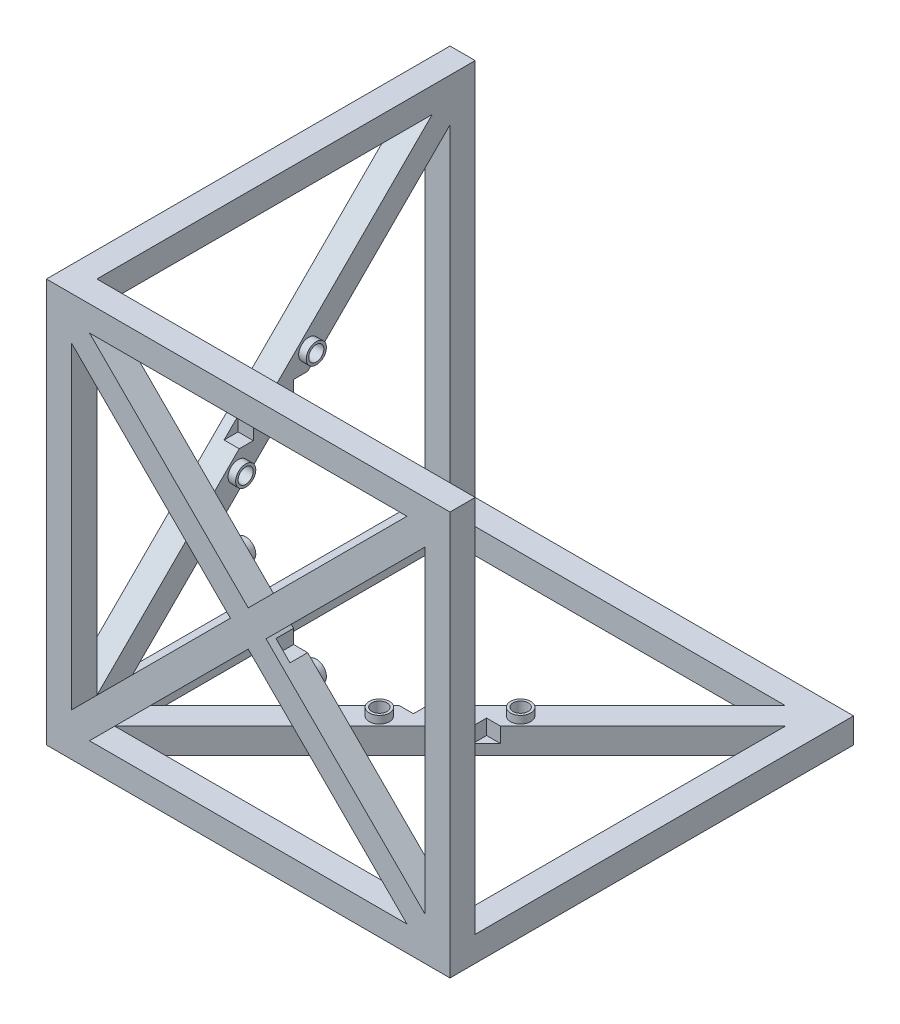
SolidWorks part; units mm, degrees
ref_plane "前视基准面" through (0, 0, 0) normal (0, 0, 1) x (1, 0, 0)
ref_plane "上视基准面" through (0, 0, 0) normal (0, 1, 0) x (1, 0, 0)
ref_plane "右视基准面" through (0, 0, 0) normal (1, 0, 0) x (0, 0, -1)
sketch "草图1" plane through (0, 0, 0) normal (0, 1, 0) x (1, 0, 0)
  line L0 (80, 0) -> (0, 80) construction
  line L1 (0, 0) -> (80, 0)
  line L2 (0, 0) -> (0, 80)
  line L3 (0, 80) -> (80, 80)
  line L4 (80, 0) -> (80, 80)
  line L5 (5, 5) -> (75, 5)
  line L6 (5, 5) -> (5, 75)
  line L7 (5, 75) -> (75, 75)
  line L8 (75, 5) -> (75, 75)
  line L9 (0, 0) -> (80, 80) construction
  line L10 (40, 0) -> (40, 80) construction
  line L11 (5, 71.4645) -> (71.4645, 5)
  line L12 (8.5355, 75) -> (75, 8.5355)
  line L13 (71.4645, 75) -> (5, 8.5355)
  line L14 (75, 71.4645) -> (8.5355, 5)
  point P19 (0.6414, 0.5)
  dimension "D1" = 5
  dimension "D2" = 5
  dimension "D3" = 5
  dimension "D4" = 5
  dimension "D5" = 80
  dimension "D6" = 80
  dimension "D7" = 2.5
extrude "凸台-拉伸1" add sketch "草图1" along normal blind 5 contours L1 L4 L3 L2 L8 L5 L6 L7 | L14 L11 L13 L6 L5 | L12 L14 L11 L5 L8 | L14 L8 L7 L13 L12 | L13 L12 L7 L6 L11 | L14 L12 L13 L11 region at (1.1314, 0, -40) region at (22.054, 0, -22.054) region at (57.946, 0, -22.054) region at (40, 0, -40) region at (22.054, 0, -57.946) region at (57.946, 0, -57.946)
sketch "草图2" plane through (0, 5, 0) normal (0, 1, 0) x (1, 0, 0)
  line L1 (0, 0) -> (5, 0)
  line L2 (0, 0) -> (0, 5)
  line L3 (0, 5) -> (5, 5)
  line L4 (5, 0) -> (5, 5)
  line L5 (80, 0) -> (75, 0)
  line L6 (80, 0) -> (80, 5)
  line L7 (80, 5) -> (75, 5)
  line L8 (75, 0) -> (75, 5)
  line L9 (0, 80) -> (5, 80)
  line L10 (0, 80) -> (0, 75)
  line L11 (0, 75) -> (5, 75)
  line L12 (5, 80) -> (5, 75)
  line L13 (5, 8.5355) -> (5, 71.4645) construction
  line L14 (8.5355, 5) -> (71.4645, 5) construction
  line L15 (75, 8.5355) -> (75, 71.4645) construction
  line L16 (8.5355, 75) -> (71.4645, 75) construction
  point P15 (0, 0)
  point P18 (0, 0)
  point P25 (0, 0)
  point P26 (0, 0)
extrude "凸台-拉伸2" add sketch "草图2" along normal blind 75
sketch "草图4" plane through (5, 0, 0) normal (1, 0, 0) x (0, 0, -1)
  line L0 (0, 80) -> (0, 5) construction
  line L1 (5, 80) -> (0, 80)
  line L2 (5, 80) -> (5, 75)
  line L3 (5, 75) -> (0, 75)
  line L4 (0, 80) -> (0, 75)
  dimension "D1" = 5
extrude "凸台-拉伸3" add sketch "草图4" along normal up to surface (70 mm away) up to face at (75, 42.5, -2.5)
sketch "草图6" plane through (0, 0, 0) normal (0, 0, 1) x (1, 0, 0)
  line L0 (5, 5) -> (75, 5) construction
  line L1 (75, 75) -> (75, 5) construction
  line L2 (5, 75) -> (5, 5) construction
  line L3 (75, 75) -> (5, 75) construction
  line L4 (5, 5) -> (75, 5)
  line L5 (75, 75) -> (75, 5)
  line L6 (5, 75) -> (5, 5)
  line L7 (75, 75) -> (5, 75)
  line L8 (5, 75) -> (75, 5) construction
  line L9 (5, 5) -> (75, 75) construction
  line L10 (40, 75) -> (40, 5) construction
  line L11 (5, 71.4645) -> (71.4645, 5)
  line L12 (8.5355, 75) -> (75, 8.5355)
  line L13 (71.4645, 75) -> (5, 8.5355)
  line L14 (75, 71.4645) -> (8.5355, 5)
  line M10 (5, 75) -> (75, 75)
  line M11 (75, 75) -> (75, 5)
  line M12 (75, 5) -> (5, 5)
  line M13 (5, 5) -> (5, 75)
  dimension "D1" = 2.5
extrude "凸台-拉伸4" add sketch "草图6" against normal up to surface (5 mm away) contours L13 L12 L6 L11 M10 | L14 L13 L12 M11 M10 | L14 L11 L13 M13 M12 | L14 L12 L13 L11 | L12 L14 L11 L5 M12 region at (22.054, 22.054, 0) region at (57.946, 22.054, 0) region at (40, 40, 0) region at (22.054, 57.946, 0) region at (57.946, 57.946, 0) up to face at (40, 41.25, -5)
sketch "草图7" plane through (0, 0, -5) normal (0, 0, -1) x (-1, 0, 0)
  line L0 (-71.4645, 75) -> (-8.5355, 75) construction
  line L1 (0, 80) -> (-5, 80)
  line L2 (0, 80) -> (0, 75)
  line L3 (0, 75) -> (-5, 75)
  line L4 (-5, 80) -> (-5, 75)
  line L5 (-5, 71.4645) -> (-5, 8.5355) construction
extrude "凸台-拉伸5" add sketch "草图7" along normal up to surface (70 mm away) up to face at (2.5, 42.5, -75)
sketch "草图8" plane through (0, 0, 0) normal (-1, 0, 0) x (0, 0, 1)
  line L0 (-75, 75) -> (-75, 5) construction
  line L1 (-5, 5) -> (-75, 5) construction
  line L2 (-5, 75) -> (-5, 5) construction
  line L3 (-75, 75) -> (-5, 75) construction
  line L4 (-75, 75) -> (-75, 5)
  line L5 (-5, 5) -> (-75, 5)
  line L6 (-5, 75) -> (-5, 5)
  line L7 (-75, 75) -> (-5, 75)
  line L8 (-75, 75) -> (-5, 5) construction
  line L9 (-5, 75) -> (-75, 5) construction
  line L10 (-40, 75) -> (-40, 5) construction
  line L11 (-75, 71.4645) -> (-8.5355, 5)
  line L12 (-71.4645, 75) -> (-5, 8.5355)
  line L13 (-5, 71.4645) -> (-71.4645, 5)
  line L14 (-8.5355, 75) -> (-75, 8.5355)
  line M10 (-75, 75) -> (-5, 75)
  line M11 (-5, 75) -> (-5, 5)
  line M12 (-5, 5) -> (-75, 5)
  line M13 (-75, 5) -> (-75, 75)
  dimension "D1" = 2.5
extrude "凸台-拉伸6" add sketch "草图8" against normal up to surface (5 mm away) contours L14 L12 L13 M10 M11 | L12 L14 L11 L13 | L12 L13 L11 L6 M12 | L14 L12 L4 L11 M10 | L11 L14 L13 M13 M12 region at (0, 57.946, -57.946) region at (0, 22.054, -57.946) region at (0, 40, -40) region at (0, 57.946, -22.054) region at (0, 22.054, -22.054) up to face at (5, 40, -2.5)
sketch "草图11" plane through (0, 5, 0) normal (0, 1, 0) x (1, 0, 0)
  line L0 (80, 80) -> (0, 0) construction
  line L1 (40, 40) -> (56.7302, 40) construction
  line L2 (40, 40) -> (40, 54.2719) construction
  line L3 (31, 43.25) -> (36, 43.25)
  line L5 (31, 43.25) -> (31, 36.75)
  line L6 (31, 36.75) -> (36, 36.75)
  line L7 (36, 43.25) -> (36, 36.75)
  line L8 (49, 43.25) -> (49, 36.75)
  line L9 (49, 36.75) -> (44, 36.75)
  line L10 (44, 43.25) -> (44, 36.75)
  line L11 (49, 43.25) -> (44, 43.25)
  circle A0 centre (47, 47) radius 1.5
  circle A1 centre (47, 33) radius 1.5
  circle A2 centre (33, 33) radius 1.5
  circle A3 centre (33, 47) radius 1.5
  circle A4 centre (47, 47) radius 2
  circle A5 centre (47, 33) radius 2
  circle A6 centre (33, 33) radius 2
  circle A7 centre (33, 47) radius 2
  circle A8 centre (40, 40) radius 1.5
  point P5 (40, 40)
  line M3 (75, 8.5355) -> (43.5355, 40)
  line M4 (43.5355, 40) -> (75, 71.4645)
  line M9 (36.4645, 40) -> (5, 8.5355)
  line M18 (5, 71.4645) -> (36.4645, 40)
  dimension "D1" = 3
  dimension "D3" = 4
  dimension "D7" = 3
  dimension "D2" = 14
  dimension "D4" = 6.5
  dimension "D5" = 5
  dimension "D6" = 4
extrude "凸台-拉伸7" add sketch "草图11" along normal blind 1.5 contours A4 A0 | A5 A1 | A6 A2 | A7 A3 region at (45.0566, 5, -47) region at (45.0566, 5, -33) region at (31.0566, 5, -33) region at (31.0566, 5, -47)
extrude "切除-拉伸1" cut sketch "草图11<2>" against normal offset from surface (3 mm away) 2 contours A3 | A2 | L7 L6 M9 | L7 L3 M18 | L11 L10 M4 | L10 L9 M3 | A0 | A1 | A8 region at (35.0715, 5, -42.3215) region at (35.0715, 5, -37.6785) region at (44.9285, 5, -42.3215) region at (44.9285, 5, -37.6785) region at (47, 5, -47) region at (47, 5, -33) region at (33, 5, -33) region at (33, 5, -47) region at (40, 5, -40) up to face at (40, 0, -15.4882)
sketch "草图11<2>" plane through (0, 5, 0) normal (0, 1, 0) x (1, 0, 0) same geometry as "草图11"
sketch "草图12" plane through (0, 0, -5) normal (0, 0, -1) x (-1, 0, 0)
  line L0 (0, 80) -> (-80, 0) construction
  line L1 (-40, 40) -> (-11.907, 40) construction
  line L2 (-40, 40) -> (-40, 67.3494) construction
  line L3 (-36, 43.25) -> (-36, 36.75)
  line L4 (-49, 43.25) -> (-44, 43.25)
  line L5 (-49, 43.25) -> (-49, 36.75)
  line L6 (-49, 36.75) -> (-44, 36.75)
  line L7 (-44, 43.25) -> (-44, 36.75)
  line L8 (-31, 36.75) -> (-36, 36.75)
  line L9 (-31, 43.25) -> (-31, 36.75)
  line L10 (-31, 43.25) -> (-36, 43.25)
  circle A0 centre (-33, 47) radius 1.5
  circle A1 centre (-33, 47) radius 2
  circle A2 centre (-33, 33) radius 1.5
  circle A3 centre (-33, 33) radius 2
  circle A4 centre (-47, 33) radius 2
  circle A5 centre (-47, 33) radius 1.5
  circle A6 centre (-47, 47) radius 2
  circle A7 centre (-47, 47) radius 1.5
  circle A8 centre (-40, 40) radius 1.5
  line M10 (-75, 71.4645) -> (-43.5355, 40)
  line M11 (-43.5355, 40) -> (-75, 8.5355)
  line M12 (-36.4645, 40) -> (-5, 71.4645)
  line M21 (-5, 8.5355) -> (-36.4645, 40)
  dimension "D1" = 3
  dimension "D2" = 4
  dimension "D8" = 3
  dimension "D3" = 14
  dimension "D4" = 5
  dimension "D5" = 6.5
  dimension "D6" = 4
  dimension "D7" = 3.25
extrude "凸台-拉伸8" add sketch "草图12" along normal blind 1.5 contours A6 A7 | A1 A0 | A3 A2 | A4 A5 region at (34.9434, 47, -5) region at (34.9434, 33, -5) region at (48.9434, 33, -5) region at (48.9434, 47, -5)
extrude "切除-拉伸2" cut sketch "草图12<2>" against normal offset from surface (3.5 mm away) 1.5 contours A5 | A2 | A0 | A7 | L7 L4 M10 | L7 L6 M11 | L8 L3 M21 | L10 L3 M12 | A8 region at (35.0715, 42.3215, -5) region at (35.0715, 37.6785, -5) region at (44.9285, 42.3215, -5) region at (44.9285, 37.6785, -5) region at (33, 47, -5) region at (33, 33, -5) region at (47, 33, -5) region at (47, 47, -5) region at (40, 40, -5) up to face at (15.4882, 40, 0)
sketch "草图12<2>" plane through (0, 0, -5) normal (0, 0, -1) x (-1, 0, 0) same geometry as "草图12"
sketch "草图13" plane through (5, 0, 0) normal (1, 0, 0) x (0, 0, -1)
  line L0 (80, 80) -> (0, 0) construction
  line L1 (40, 40) -> (55.0072, 40) construction
  line L2 (40, 40) -> (40, 57.8496) construction
  line L3 (44, 43.25) -> (44, 36.75)
  line L4 (31, 43.25) -> (36, 43.25)
  line L5 (31, 43.25) -> (31, 36.75)
  line L6 (31, 36.75) -> (36, 36.75)
  line L7 (36, 43.25) -> (36, 36.75)
  line L8 (49, 36.75) -> (44, 36.75)
  line L9 (49, 43.25) -> (49, 36.75)
  line L10 (49, 43.25) -> (44, 43.25)
  circle A0 centre (47, 47) radius 1.5
  circle A1 centre (47, 47) radius 2
  circle A2 centre (47, 33) radius 2
  circle A3 centre (47, 33) radius 1.5
  circle A4 centre (33, 33) radius 1.5
  circle A5 centre (33, 33) radius 2
  circle A6 centre (33, 47) radius 2
  circle A7 centre (33, 47) radius 1.5
  circle A8 centre (40, 40) radius 1.5
  line M11 (5, 71.4645) -> (36.4645, 40)
  line M12 (36.4645, 40) -> (5, 8.5355)
  line M16 (43.5355, 40) -> (75, 71.4645)
  line M18 (75, 8.5355) -> (43.5355, 40)
  dimension "D1" = 4
  dimension "D2" = 3
  dimension "D8" = 3
  dimension "D3" = 14
  dimension "D4" = 5
  dimension "D5" = 6.5
  dimension "D6" = 3.25
  dimension "D7" = 4
extrude "凸台-拉伸9" add sketch "草图13" along normal blind 1.5 contours A6 A7 | A1 A0 | A5 A4 | A2 A3 region at (5, 47, -45.0566) region at (5, 33, -45.0566) region at (5, 33, -31.0566) region at (5, 47, -31.0566)
extrude "切除-拉伸3" cut sketch "草图13<2>" against normal offset from surface (3 mm away) 2 contours A4 | A7 | A0 | A3 | L7 L4 M11 | L7 L6 M12 | L8 L3 M18 | L10 L3 M16 | A8 region at (5, 42.3215, -44.9285) region at (5, 37.6785, -44.9285) region at (5, 42.3215, -35.0715) region at (5, 37.6785, -35.0715) region at (5, 47, -47) region at (5, 33, -47) region at (5, 33, -33) region at (5, 47, -33) region at (5, 40, -40) up to face at (0, 40, -15.4882)
sketch "草图13<2>" plane through (5, 0, 0) normal (1, 0, 0) x (0, 0, -1) same geometry as "草图13"
